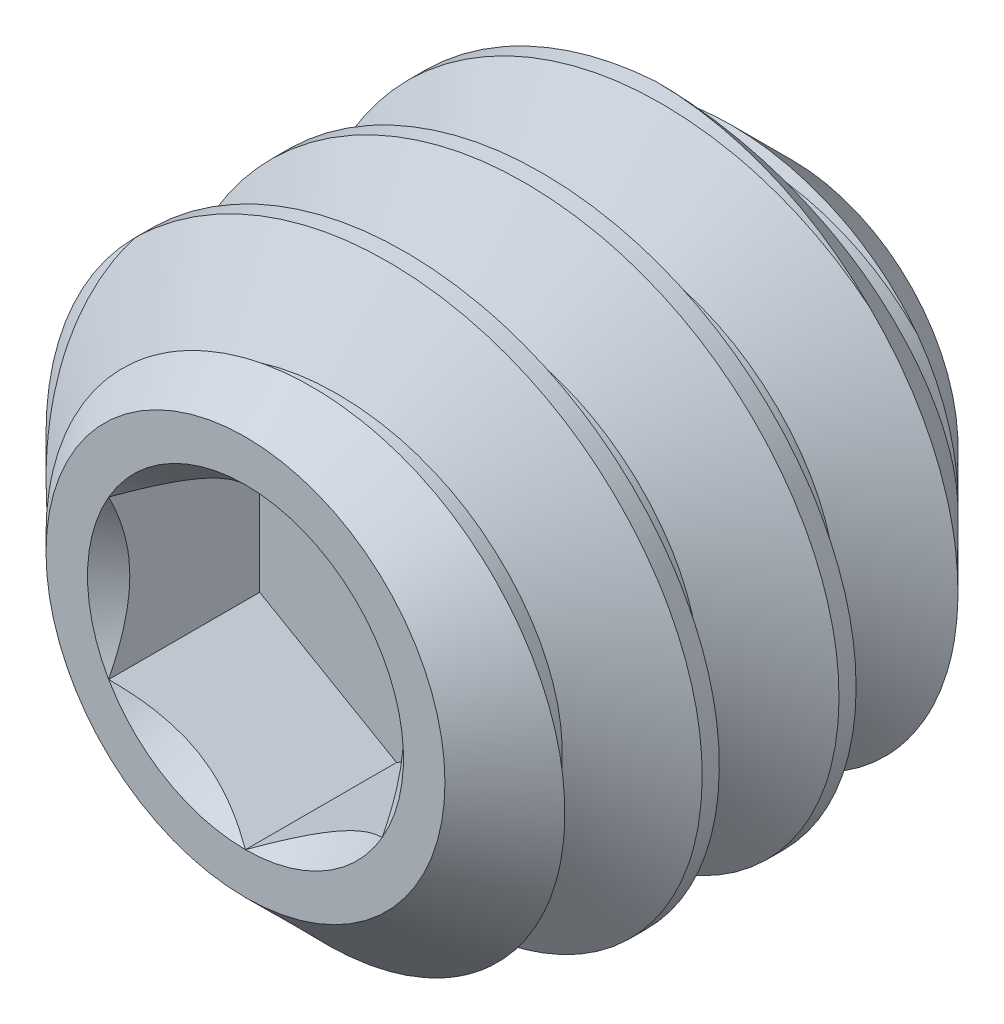
SolidWorks part; units mm, degrees
ref_plane "Front Plane" through (0, 0, 0) normal (0, 0, 1) x (1, 0, 0)
ref_plane "Top Plane" through (0, 0, 0) normal (0, 1, 0) x (1, 0, 0)
ref_plane "Right Plane" through (0, 0, 0) normal (1, 0, 0) x (0, 0, -1)
sketch "Sketch1" plane through (0, 0, 0) normal (1, 0, 0) x (0, 0, -1)
  line L6 (-1.5875, 0) -> (1.5875, 0) construction
  line L7 (-1.5875, 0) -> (-1.5875, 1.7526)
  line L8 (-1.5875, 1.7526) -> (1.5875, 1.7526)
  line L9 (1.5875, 1.7526) -> (1.5875, 0)
  line L10 (1.5379, 1.8385) -> (1.9348, 1.1511) construction
  line L15 (1.9348, 1.1511) -> (2.3316, 1.8385) construction
  line L16 (2.3316, 1.8385) -> (1.5379, 1.8385) construction
  line L17 (1.5627, 1.7956) -> (2.3068, 1.7956)
  line L18 (2.3068, 1.7956) -> (1.9844, 1.237)
  line L19 (1.9844, 1.237) -> (1.8852, 1.237)
  line L20 (1.8852, 1.237) -> (1.5627, 1.7956)
  line L21 (1.9348, 1.237) -> (1.9348, 1.1511) construction
  line L22 (1.5875, 1.7526) -> (2.282, 1.7526) construction
  line L23 (1.9348, 1.8385) -> (1.9348, 1.7526) construction
  line L24 (0.7937, 1.7526) -> (1.5875, 0.9589)
  line L25 (-1.5875, 1.1573) -> (-0.9922, 1.7526)
  line L26 (1.5875, 0.9092) -> (1.0412, 0)
  line L27 (1.5875, -0.9092) -> (1.0412, 0)
  point P4 (0, 0)
  point P23 (1.9348, 1.7956)
  point P29 (-0.7112, 0)
  point P30 (0.3969, 1.7526)
  point P31 (0.3969, -1.7526)
  point P32 (-1.5875, -1.7526)
  dimension "Length" = 3.175
  dimension "Screw Size Decimal Equivalent" = 3.5052
  dimension "Pitch" = 0.7937
  dimension "D2" = 0.0992
  dimension "D3" = 0.7937
  dimension "D1" = 45
  dimension "D4" = 0.5953
  dimension "D5" = 59
  dimension "D6" = 0.0496
  dimension "D7" = 0.8763
  dimension "D8" = 1.1906
sketch "Sketch10" plane through (0, 0, 0) normal (0, 0, 1) x (1, 0, 0)
  line L1 (0, 0.9165) -> (-0.7938, 0.4583)
  line L2 (-0.7938, 0.4583) -> (-0.7938, -0.4583)
  line L3 (-0.7938, -0.4583) -> (0, -0.9165)
  line L4 (0, -0.9165) -> (0.7937, -0.4583)
  line L5 (0.7937, -0.4583) -> (0.7937, 0.4583)
  line L6 (0.7937, 0.4583) -> (0, 0.9165)
  circle A0 centre (0, 0) radius 0.7938 construction
  dimension "Drive Size" = 1.5875
sketch "Sketch2" plane through (0, 0, 0) normal (1, 0, 0) x (0, 0, -1)
  line L10 (1.5875, 0.9092) -> (1.0412, 0) construction
  line L18 (-1.5875, 1.1573) -> (-0.9922, 1.7526) construction
  line L20 (1.5875, 0.9092) -> (1.0412, 0)
  line L21 (-1.5875, 1.1573) -> (-0.9922, 1.7526)
  line L22 (-0.9922, 1.7526) -> (1.5875, 1.7526)
  line L23 (1.5875, 1.7526) -> (1.5875, 0.9092)
  line L24 (1.0412, 0) -> (-1.5875, 0)
  line L25 (-1.5875, 0) -> (-1.5875, 1.1573)
revolve "Revolve1" add sketch "Sketch2" angle 360 about L24
chamfer "Chamfer1" distance 0.7937 angle 45 1 edges at (0, 1.7526, -1.5875)
sketch "Sketch3" plane through (0, 0, 1.5875) normal (0, 0, 1) x (1, 0, 0)
  line L0 (-0.7938, -0.4583) -> (0, -0.9165) construction
  line L7 (-0.7938, 0.4583) -> (-0.7938, -0.4583) construction
  line L8 (0, 0.9165) -> (-0.7938, 0.4583) construction
  line L9 (0.7937, 0.4583) -> (0, 0.9165) construction
  line L10 (0.7937, -0.4583) -> (0.7937, 0.4583) construction
  line L11 (0, -0.9165) -> (0.7937, -0.4583) construction
  line L12 (-0.7938, -0.4583) -> (0, -0.9165)
  line L13 (-0.7938, 0.4583) -> (-0.7938, -0.4583)
  line L14 (0, 0.9165) -> (-0.7938, 0.4583)
  line L15 (0.7937, 0.4583) -> (0, 0.9165)
  line L16 (0.7937, -0.4583) -> (0.7937, 0.4583)
  line L17 (0, -0.9165) -> (0.7937, -0.4583)
extrude "Cut-Extrude1" cut sketch "Sketch3" against normal up to vertex (0.8763 mm away) up to point (0, 0, 0.7112)
sketch "Sketch4" plane through (0, 0, 1.5875) normal (0, 0, 1) x (1, 0, 0)
  circle A1 centre (0, 0) radius 0.9165
extrude "Cut-Extrude2" cut sketch "Sketch4" against normal up to vertex (0.8763 mm away) draft 45 up to point (0, 0, 0.7112)
ref_axis "Center Axis 1" through (0, 0, -1.7801) along (0, 0, 1)
sketch "Sketch7" plane through (0, 0, -1.5875) normal (0, 0, -1) x (-1, 0, 0)
  circle A3 centre (0, 0) radius 1.7526 construction
  circle A4 centre (0, 0) radius 1.7526
curve "Helix/Spiral1" pitch 0.7937 height 3.9767 radius 1.7526 centre (0, 0, -1.5875) axis (0, 0, 1) start towards (0, 1, 0)
sketch "Sketch8" plane through (0, 0, 0) normal (1, 0, 0) x (0, 0, -1)
  line L0 (1.9844, 1.237) -> (1.8852, 1.237) construction
  line L1 (2.3068, 1.7956) -> (1.9844, 1.237) construction
  line L2 (1.5627, 1.7956) -> (2.3068, 1.7956) construction
  line L3 (1.8852, 1.237) -> (1.5627, 1.7956) construction
  line L4 (1.9844, 1.237) -> (1.8852, 1.237)
  line L5 (2.3068, 1.7956) -> (1.9844, 1.237)
  line L6 (1.5627, 1.7956) -> (2.3068, 1.7956)
  line L7 (1.8852, 1.237) -> (1.5627, 1.7956)
sweep "Cut-Sweep1" cut profiles "Sketch8" path "Helix/Spiral1"
equation "\"D3@Helix/Spiral1\"=\"Length@Sketch1\"+(\"Pitch@Sketch1\"*1.01)"
equation "\"D4@Helix/Spiral1\"=\"Pitch@Sketch1\""
equation "\"D2@Sketch1\" = \"Pitch@Sketch1\" / 8"
equation "\"D3@Sketch1\"=\"Pitch@Sketch1\""
equation "\"D4@Sketch1\"=\"Pitch@Sketch1\"*0.75"
equation "\"D6@Sketch1\"=\"D2@Sketch1\"/2"
equation "\"D7@Sketch1\"=0.25*\"Screw Size Decimal Equivalent@Sketch1\""
equation "\"D1@Chamfer1\"=\"D3@Sketch1\""
equation "\"D8@Sketch1\"=\"Pitch@Sketch1\"*1.5"
